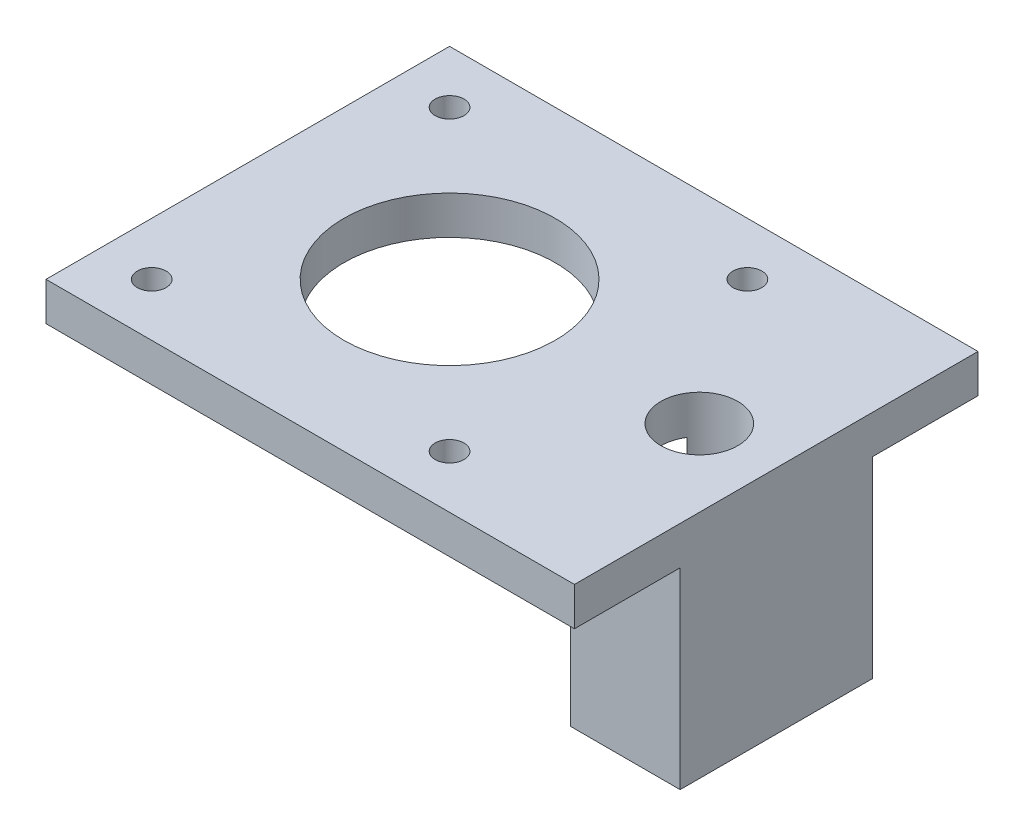
SolidWorks part; units mm, degrees
ref_plane "Front Plane" through (0, 0, 0) normal (0, 0, 1) x (1, 0, 0)
ref_plane "Top Plane" through (0, 0, 0) normal (0, 1, 0) x (1, 0, 0)
ref_plane "Right Plane" through (0, 0, 0) normal (1, 0, 0) x (0, 0, -1)
sketch "Sketch1" plane through (0, 0, 0) normal (0, 1, 0) x (1, 0, 0)
  line L0 (0, 21) -> (55, 21) construction
  line L1 (0, 0) -> (55, 0)
  line L2 (0, 0) -> (0, 42)
  line L3 (0, 42) -> (55, 42)
  line L4 (55, 0) -> (55, 42)
  line L5 (21, 42) -> (21, 0) construction
  circle A0 centre (47, 21) radius 4
  circle A1 centre (21, 21) radius 11
  circle A2 centre (5.5, 36.5) radius 1.5
  circle A3 centre (36.5, 36.5) radius 1.5
  circle A4 centre (5.5, 5.5) radius 1.5
  circle A5 centre (36.5, 5.5) radius 1.5
  point P8 (55, 21)
  point P14 (27.5, 42)
  point P15 (21, 42)
  dimension "D2" = 22
  dimension "D4" = 8
  dimension "D9" = 3
  dimension "D1" = 26
  dimension "D3" = 42
  dimension "D5" = 21
  dimension "D6" = 55
  dimension "D7" = 15.5
  dimension "D8" = 15.5
extrude "Boss-Extrude1" add sketch "Sketch1" along normal blind 4
sketch "Sketch2" plane through (0, 0, 0) normal (0, -1, 0) x (1, 0, 0)
  line L0 (0, 0) -> (55, 0) construction
  line L1 (40.6, 0) -> (43.6, 0)
  line L2 (40.6, 0) -> (40.6, -42)
  line L3 (40.6, -42) -> (43.6, -42)
  line L4 (43.6, 0) -> (43.6, -42)
  line L5 (55, -42) -> (0, -42) construction
  line L6 (55, 0) -> (55, -42) construction
  line L7 (55, -11) -> (43.6, -11)
  line L8 (55, -11) -> (55, -31)
  line L9 (55, -31) -> (43.6, -31)
  line L10 (43.6, -11) -> (43.6, -31)
  circle A0 centre (47, -21) radius 6.4
  circle A1 centre (47, -21) radius 4
  circle A2 centre (47, -21) radius 4 construction
  point P20 (0, 0)
  point P21 (43.6, -11.8093)
  point P22 (43.6, -29.8054)
  point P23 (55, -35.3455)
  point P24 (55, -27.4224)
  point P25 (55, -21)
  point P26 (55, -21)
  circle M7 centre (47, -21) radius 4
  line M10 (55, -42) -> (55, 0)
  dimension "D1" = 2.4
  dimension "D2" = 3
  dimension "D3" = 20
extrude "Boss-Extrude2" add sketch "Sketch2" along normal blind 20 contours L4 A0 L10 M7 | A0 L10 L9 L7 L4 M10 region at (49.3, 0, -11.2302) region at (50.0203, 0, -15.5411)
equation "\"8mm hole\" = 8mm"
equation "\"22mm hole\"= 22mm"
equation "\"D2@Sketch1\"=\"22mm hole\""
equation "\"D4@Sketch1\"=\"8mm hole\""
